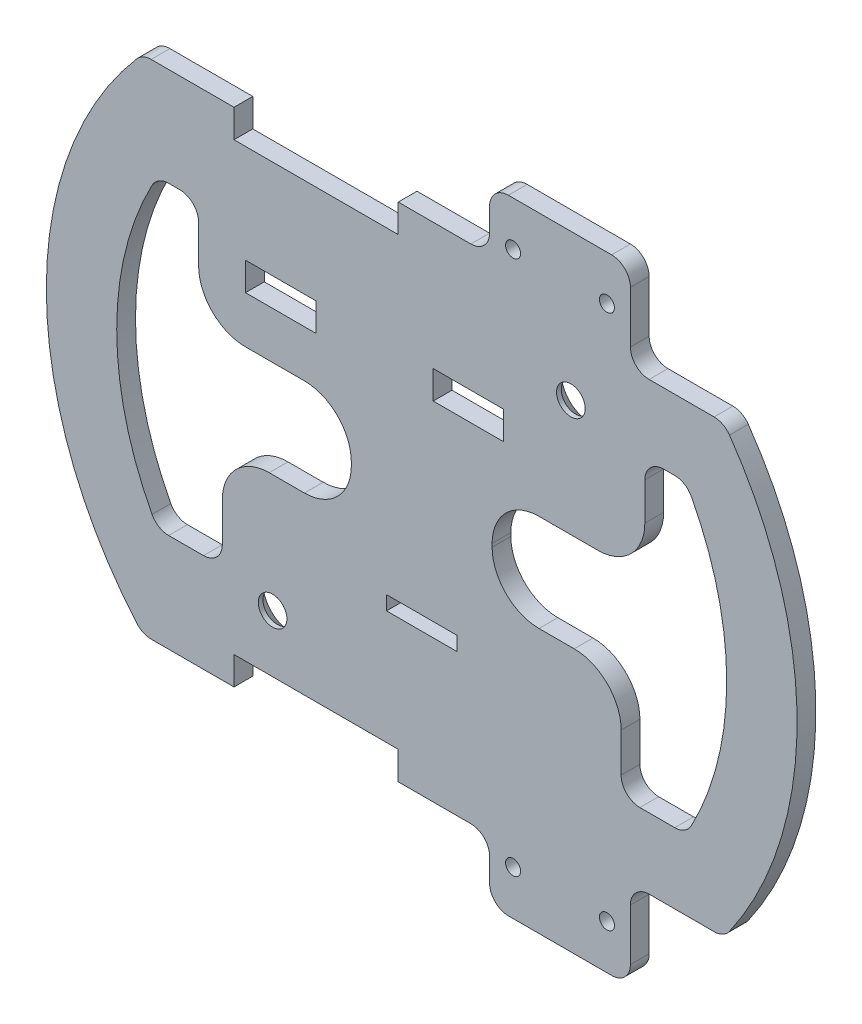
SolidWorks part; units mm, degrees
material "Acrílico (médio-alto impacto)"
ref_plane "Plano frontal" through (0, 0, 0) normal (0, 0, 1) x (1, 0, 0)
ref_plane "Plano superior" through (0, 0, 0) normal (0, 1, 0) x (1, 0, 0)
ref_plane "Plano direito" through (0, 0, 0) normal (1, 0, 0) x (0, 0, -1)
sketch "Esboço1" plane through (0, 0, 0) normal (0, 0, 1) x (1, 0, 0)
  line L0 (80, 0) -> (0, 0) construction
  line L1 (-80, -66.5) -> (80, -66.5)
  line L2 (-80, -66.5) -> (-80, 66.5)
  line L3 (-80, 66.5) -> (80, 66.5)
  line L4 (80, -66.5) -> (80, 66.5)
  line L5 (-80, -66.5) -> (80, 66.5) construction
  line L6 (-80, 66.5) -> (80, -66.5) construction
  line L7 (80, 47.5) -> (-80, 47.5) construction
  line L8 (80, -47.5) -> (-80, -47.5) construction
  line L9 (14.4719, 66.5) -> (14.4719, 53.5)
  line L10 (0, 0) -> (0, 66.5) construction
  line L11 (44.4719, 47.5) -> (44.4719, 66.5)
  line L12 (44.4719, -47.5) -> (44.4719, -66.5)
  line L13 (14.4719, -66.5) -> (14.4719, -53.5)
  line L14 (14.4719, 53.5) -> (-59.479, 53.5)
  line L15 (14.4719, -53.5) -> (-59.479, -53.5)
  line L16 (-5.0035, 47.5) -> (-40.0035, 47.5)
  line L17 (-5.0035, 47.5) -> (-5.0035, 53.5)
  line L18 (-31.7837, -35.2994) -> (31.7837, 35.2994) construction
  line L19 (-42.5, -20.2) -> (-42.5, -14.2) construction
  line L20 (-7.5, -20.2) -> (7.5, -20.2)
  line L21 (-7.5, -20.2) -> (-7.5, -23.2)
  line L22 (-7.5, -23.2) -> (7.5, -23.2)
  line L23 (7.5, -20.2) -> (7.5, -23.2)
  line L24 (-7.5, -20.2) -> (7.5, -23.2) construction
  line L25 (-7.5, -23.2) -> (7.5, -20.2) construction
  line L26 (-37.55, 26.5) -> (-22.55, 26.5)
  line L27 (-37.55, 26.5) -> (-37.55, 20.5)
  line L28 (-37.55, 20.5) -> (-22.55, 20.5)
  line L29 (-22.55, 26.5) -> (-22.55, 20.5)
  line L30 (-37.55, 26.5) -> (-22.55, 20.5) construction
  line L31 (-37.55, 20.5) -> (-22.55, 26.5) construction
  line L32 (17.45, 20.5) -> (2.45, 20.5)
  line L33 (17.45, 20.5) -> (17.45, 26.5)
  line L34 (17.45, 26.5) -> (2.45, 26.5)
  line L35 (2.45, 20.5) -> (2.45, 26.5)
  line L36 (17.45, 20.5) -> (2.45, 26.5) construction
  line L37 (17.45, 26.5) -> (2.45, 20.5) construction
  line L38 (-42.5, -14.2) -> (42.5, -14.2) construction
  line L39 (42.5, -14.2) -> (42.5, -20.2) construction
  line L40 (42.5, -20.2) -> (-42.5, -20.2) construction
  line L41 (-56.2917, 32.5) -> (-47.55, 32.5)
  line L42 (-47.55, 32.5) -> (-47.55, 10.5)
  line L43 (-47.55, 10.5) -> (-15, 10.5)
  line L44 (-15, 10.5) -> (-15, -10.2)
  line L47 (-42.5, -32.5) -> (-56.2917, -32.5)
  line L48 (-42.5, -32.5) -> (-42.5, -10.2)
  line L49 (-42.5, -10.2) -> (-15, -10.2)
  line L50 (15, -10.2) -> (15, 10.5)
  line L51 (15, 10.5) -> (47.55, 10.5)
  line L52 (47.55, 10.5) -> (47.55, 32.5)
  line L53 (47.55, 32.5) -> (56.2917, 32.5)
  line L54 (56.2917, -32.5) -> (42.5, -32.5)
  line L55 (15, -10.2) -> (42.5, -10.2)
  line L56 (42.5, -10.2) -> (42.5, -32.5)
  line L57 (15, 10.5) -> (-15, 10.5) construction
  line L58 (-21.0674, -35.2994) -> (-42.5, -35.2994) construction
  line L59 (-5.0035, 53.5) -> (-40.0035, 53.5)
  line L60 (-40.0035, 47.5) -> (-40.0035, 53.5)
  line L61 (-5.0035, 47.5) -> (-40.0035, 53.5) construction
  line L62 (-5.0035, 53.5) -> (-40.0035, 47.5) construction
  line L63 (-5.0035, -53.5) -> (-40.0035, -53.5)
  line L64 (-40.0035, -47.5) -> (-40.0035, -53.5)
  line L65 (-5.0035, -47.5) -> (-40.0035, -47.5)
  line L66 (-5.0035, -47.5) -> (-5.0035, -53.5)
  line L67 (24.9009, 47.5) -> (24.9009, 66.5) construction
  line L69 (44.4719, 47.5) -> (64.372, 47.5)
  line L70 (44.4719, -47.5) -> (64.372, -47.5)
  line L73 (-56.2917, 32.5) -> (-56.2917, 53.5)
  line L74 (-56.2917, -32.5) -> (-56.2917, -56.8441)
  line L75 (56.2917, 32.5) -> (56.2917, 47.5)
  line L76 (56.2917, -32.5) -> (56.2917, -56.8441)
  circle A0 centre (0, 0) radius 80
  circle A1 centre (-31.7837, -35.2994) radius 3.05
  circle A2 centre (31.7837, 35.2994) radius 3.05
  circle A3 centre (19.4719, 57) radius 1.6
  circle A8 centre (19.4719, -57) radius 1.6
  arc A9 (-56.2917, -32.5) -> (-56.2917, 32.5) centre (0, 0) cw
  arc A10 (56.2917, -32.5) -> (56.2917, 32.5) centre (0, 0) ccw
  circle A11 centre (39.4719, 57) radius 1.6
  circle A12 centre (39.4719, -57) radius 1.6
  point P0 (0, 0)
  point P17 (-22.5035, 50.5)
  point P22 (44.4719, 66.5)
  point P34 (-30.05, 23.5)
  point P44 (0, -21.7)
  point P53 (9.95, 23.5)
  point P58 (0, -20.2)
  point P65 (-65, 0)
  point P80 (0, 10.5)
  point P83 (24.9009, 57)
  point P84 (-22.5035, 53.5)
  dimension "D6" = 6.1
  dimension "D7" = 6
  dimension "D18" = 15
  dimension "D25" = 3.2
  dimension "D1" = 95
  dimension "D2" = 19
  dimension "D3" = 160
  dimension "D4" = 95
  dimension "D5" = 48
  dimension "D8" = 5
  dimension "D9" = 3
  dimension "D10" = 6
  dimension "D11" = 15
  dimension "D12" = 20.2
  dimension "D13" = 40.7
  dimension "D14" = 25
  dimension "D15" = 2.45
  dimension "D16" = 85
  dimension "D17" = 35
  dimension "D19" = 10
  dimension "D20" = 10
  dimension "D21" = 10
  dimension "D22" = 30
  dimension "D23" = 30
  dimension "D24" = 5
  dimension "D26" = 15
extrude "Ressalto-extrusão1" add sketch "Esboço1" along normal blind 4 contours L74 A9 L73 L14 A0 L15 | L76 L54 L56 L55 L50 L51 L52 L53 L75 L69 L11 L3 L9 L14 L17 L16 L60 L73 L41 L42 L43 L44 L49 L48 L47 L74 L15 L64 L65 L66 L13 L1 L12 L70 A8 A3 A2 A1 L20 L23 L22 L21 L26 | A10 L76 L70 A0 L69 L75 region at (2.8306, 0.1464, 0) region at (67.9724, 0, 0) region at (-67.5674, 0, 0)
chamfer "Chanfro1" distance 3 angle 45 2 edges at (34.8337, 35.2994, 0) (-28.7337, -35.2994, 0)
fillet "Filete1" radius 4 20 edges at (56.2917, 32.5, 2) (47.55, 32.5, 2) (42.5, -32.5, 2) (56.2917, -32.5, 2) (-42.5, -32.5, 2) (-56.2917, -32.5, 2) (-47.55, 32.5, 2) (-56.2917, 32.5, 2) (14.4719, -53.5, 2) (14.4719, 53.5, 2) (44.4719, 47.5, 2) (44.4719, -47.5, 2) (14.4719, 66.5, 2) (44.4719, 66.5, 2) (44.4719, -66.5, 2) (14.4719, -66.5, 2) (-59.479, 53.5, 2) (64.372, 47.5, 2) (64.372, -47.5, 2) (-59.479, -53.5, 2)
fillet "Filete2" radius 10 4 edges at (15, -10.2, 2) (-15, -10.2, 2) (-15, 10.5, 2) (15, 10.5, 2)
fillet "Filete3" radius 10 4 edges at (47.55, 10.5, 2) (-47.55, 10.5, 2) (42.5, -10.2, 2) (-42.5, -10.2, 2)
